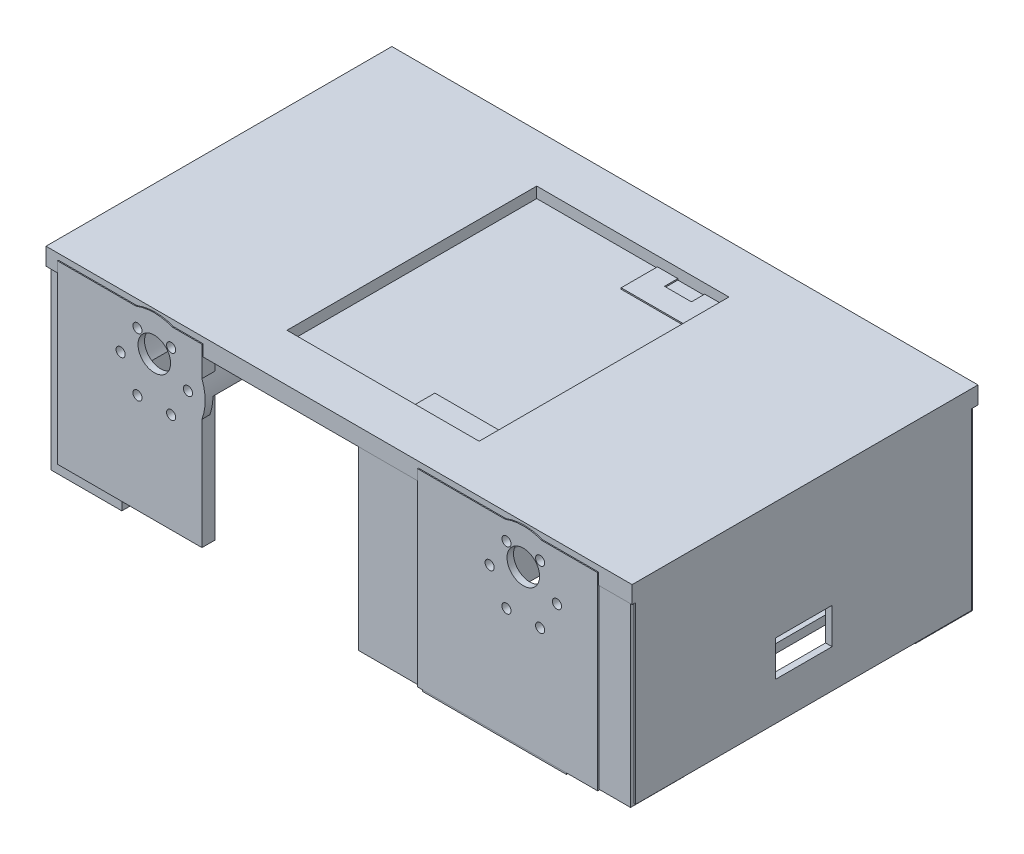
SolidWorks part; units mm, degrees
ref_plane "Front Plane" through (0, 0, 0) normal (0, 0, 1) x (1, 0, 0)
ref_plane "Top Plane" through (0, 0, 0) normal (0, 1, 0) x (1, 0, 0)
ref_plane "Right Plane" through (0, 0, 0) normal (1, 0, 0) x (0, 0, -1)
sketch "MotorHoldersSketch" plane through (0, 0, 0) normal (0, 0, 1) x (1, 0, 0)
  line L0 (0, 0) -> (170, 0) construction
  line L1 (0, 0) -> (0, 23.41) construction
  line L2 (170, 0) -> (170, 23.41) construction
  circle A0 centre (0, 0) radius 23.41
  circle A1 centre (170, 0) radius 23.41
ref_axis "MotorCenterAxis1" through (0, 0, 0) along (0, 0, 1)
ref_axis "MotorCenterAxis2" through (170, 0, 0) along (0, 0, 1)
extrude "MotorHolders" add sketch "MotorHoldersSketch" along normal blind 80 and the other way blind 80
sketch "Sketch3" plane through (0, 0, 0) normal (0, 0, 1) x (1, 0, 0)
  line L1 (1.9406, 21.133) -> (168.3435, 21.133)
  line L2 (1.9406, 21.133) -> (1.9406, 18.3155)
  line L3 (1.9406, 18.3155) -> (168.3435, 18.3155)
  line L4 (168.3435, 21.133) -> (168.3435, 18.3155)
sketch "Sketch4" plane through (0, 0, 0) normal (0, 1, 0) x (1, 0, 0)
  line L1 (221.2811, -76.3794) -> (-41.4939, -76.3794)
  line L2 (221.2811, -76.3794) -> (221.2811, 76.7331)
  line L3 (221.2811, 76.7331) -> (-41.4939, 76.7331)
  line L4 (-41.4939, -76.3794) -> (-41.4939, 76.7331)
extrude "Cut-Extrude1" cut sketch "Sketch4" against normal blind 23
ref_axis "Axis3" through (170, 0, 0) along (0, -1, 0)
sketch3d "ReferencePlanePosition"
  line L0 (170, 0, 0) -> (170, -34.8293, 0)
  line L1 (170, 0, 0) -> (170, -38.994, 0) construction
ref_plane "ReferencePlane" through (170, -34.8293, 0) normal (0, -1, 0) x (-1, 0, 0)
sketch "Sketch6" plane through (170, -34.8293, 0) normal (0, -1, 0) x (-1, 0, 0)
  line L1 (219.5858, 78.949) -> (187.0382, 78.949)
  line L2 (219.5858, 78.949) -> (219.5858, 52.706)
  line L3 (219.5858, 52.706) -> (187.0382, 52.706)
  line L4 (187.0382, 78.949) -> (187.0382, 52.706)
  line L5 (219.3147, -52.1095) -> (186.667, -52.1095)
  line L6 (219.3147, -52.1095) -> (219.3147, -78.2822)
  line L7 (219.3147, -78.2822) -> (186.667, -78.2822)
  line L8 (186.667, -52.1095) -> (186.667, -78.2822)
  line L9 (75.6651, 77.8627) -> (19.9904, 77.8627)
  line L10 (75.6651, 77.8627) -> (75.6651, 40.7512)
  line L11 (75.6651, 40.7512) -> (19.9904, 40.7512)
  line L12 (19.9904, 77.8627) -> (19.9904, 40.7512)
  line L13 (76.5596, -44.1716) -> (20.0852, -44.1716)
  line L14 (76.5596, -44.1716) -> (76.5596, -79.4437)
  line L15 (76.5596, -79.4437) -> (20.0852, -79.4437)
  line L16 (20.0852, -44.1716) -> (20.0852, -79.4437)
  line L17 (213.765, 71.7736) -> (201.9877, 71.7736)
  line L18 (213.765, 71.7736) -> (213.765, 60.5121)
  line L19 (213.765, 60.5121) -> (201.9877, 60.5121)
  line L20 (201.9877, 71.7736) -> (201.9877, 60.5121)
  line L21 (41.3552, 69.1777) -> (28.5109, 69.1777)
  line L22 (41.3552, 69.1777) -> (41.3552, 50.8413)
  line L23 (41.3552, 50.8413) -> (28.5109, 50.8413)
  line L24 (28.5109, 69.1777) -> (28.5109, 50.8413)
  line L25 (43.3068, -72.8101) -> (32.1723, -72.8101)
  line L26 (43.3068, -72.8101) -> (43.3068, -54.7747)
  line L27 (43.3068, -54.7747) -> (32.1723, -54.7747)
  line L28 (32.1723, -72.8101) -> (32.1723, -54.7747)
  line L29 (211.9411, -70.4881) -> (201.0982, -70.4881)
  line L30 (211.9411, -70.4881) -> (211.9411, -60.1404)
  line L31 (211.9411, -60.1404) -> (201.0982, -60.1404)
  line L32 (201.0982, -70.4881) -> (201.0982, -60.1404)
  line L37 (66.2772, 51.3198) -> (53.8697, 51.3198)
  line L38 (66.2772, 51.3198) -> (66.2772, 67.7632)
  line L39 (66.2772, 67.7632) -> (53.8697, 67.7632)
  line L40 (53.8697, 51.3198) -> (53.8697, 67.7632)
  line L45 (68.2481, -69.8638) -> (51.7107, -69.8638)
  line L46 (68.2481, -69.8638) -> (68.2481, -55.4273)
  line L47 (68.2481, -55.4273) -> (51.7107, -55.4273)
  line L48 (51.7107, -69.8638) -> (51.7107, -55.4273)
  line L49 (-20.7001, -79.4437) -> (-48.8506, -79.4437)
  line L50 (-20.7001, -79.4437) -> (-20.7001, -54.5097)
  line L51 (-20.7001, -54.5097) -> (-48.8506, -54.5097)
  line L52 (-48.8506, -79.4437) -> (-48.8506, -54.5097)
  line L53 (-18.3873, 77.8627) -> (-49.0581, 77.8627)
  line L54 (-18.3873, 77.8627) -> (-18.3873, 51.5325)
  line L55 (-18.3873, 51.5325) -> (-49.0581, 51.5325)
  line L56 (-49.0581, 77.8627) -> (-49.0581, 51.5325)
  line L57 (-41.8141, -72.8101) -> (-31.6362, -72.8101)
  line L58 (-41.8141, -72.8101) -> (-41.8141, -62.9794)
  line L59 (-41.8141, -62.9794) -> (-31.6362, -62.9794)
  line L60 (-31.6362, -72.8101) -> (-31.6362, -62.9794)
  line L61 (-31.6362, 69.1777) -> (-41.5347, 69.1777)
  line L62 (-31.6362, 69.1777) -> (-31.6362, 58.5421)
  line L63 (-31.6362, 58.5421) -> (-41.5347, 58.5421)
  line L64 (-41.5347, 69.1777) -> (-41.5347, 58.5421)
extrude "PowerBankHolders" add sketch "Sketch6" along normal blind 30 and the other way blind 55 separate body
sketch3d "3DSketch3"
  line L0 (170, 0, 0) -> (170, -64.5, 0) construction
ref_plane "Plane2" through (170, -64.5, 0) normal (0, -1, 0) x (-1, 0, 0)
sketch "Sketch7" plane through (170, -64.5, 0) normal (0, -1, 0) x (-1, 0, 0)
  line L1 (-9.5047, -80.801) -> (181.32, -80.801)
  line L2 (-9.5047, -80.801) -> (-9.5047, 73.8662)
  line L3 (-9.5047, 73.8662) -> (181.32, 73.8662)
  line L4 (181.32, -80.801) -> (181.32, 73.8662)
  line L5 (151.8712, -54.3972) -> (26.5361, -54.3972)
  line L6 (151.8712, -54.3972) -> (151.8712, 46.2413)
  line L7 (151.8712, 46.2413) -> (26.5361, 46.2413)
  line L8 (26.5361, -54.3972) -> (26.5361, 46.2413)
ref_point "Point1"
ref_point "Point2"
sketch3d "3DSketch11"
  line L0 (0, 0, -80) -> (170, 0, 80) construction
  point P4 (85, 0, 0)
sketch "MotorHolderExtrudeSketch" plane through (0, 0, 0) normal (0, 0, 1) x (1, 0, 0)
  circle A0 centre (170, 0) radius 20.415
  circle A1 centre (0, 0) radius 20.415
  circle A3 centre (0, 0) radius 23.41 construction
  circle A4 centre (170, 0) radius 23.41 construction
ref_point "TopOfMotors"
ref_plane "TangentToTopOfMotors" through (0, -20.415, 0) normal (0, 1, 0) x (1, 0, 0)
ref_axis "Axis4" through (85, 0, 0) along (0, -1, 0)
ref_plane "BottomOfPowerBankRegion" through (0, -20.425, 0) normal (0, 1, 0) x (1, 0, 0)
sketch "Sketch11" plane through (0, -20.425, 0) normal (0, 1, 0) x (1, 0, 0)
  line L0 (-18.9327, 3.7419) -> (188.9327, -3.7419) construction
  line L5 (-18.9327, -64.7581) -> (-18.9327, 72.2419)
  line L6 (188.9327, 63.7581) -> (188.9327, -71.2419)
  line L7 (188.9327, -71.2419) -> (-18.9327, -64.7581)
  line L8 (188.9327, 63.7581) -> (-18.9327, 72.2419)
  circle A0 centre (85, 0) radius 104 construction
ref_point "CenterAtBottomOfPowerBank"
ref_plane "TopOfPowerBankPlane" through (0, -54.425, 0) normal (0, 1, 0) x (1, 0, 0)
sketch "Sketch13" plane through (0, -54.425, 0) normal (0, 1, 0) x (1, 0, 0)
  line L1 (-19.4498, 72.5454) -> (166.1636, 72.5454)
  line L2 (-19.4498, 72.5454) -> (-19.4498, -78.2051)
  line L3 (-19.4498, -78.2051) -> (166.1636, -78.2051)
  line L4 (166.1636, 72.5454) -> (166.1636, -78.2051)
  line L5 (19.3173, -49.583) -> (137.9607, -49.583)
  line L6 (19.3173, -49.583) -> (19.3173, -21.0549)
  line L7 (19.3173, -21.0549) -> (137.9607, -21.0549)
  line L8 (137.9607, -49.583) -> (137.9607, -21.0549)
  line L9 (19.3173, 56.6778) -> (137.9607, 56.6778)
  line L10 (19.3173, 56.6778) -> (19.3173, 36.3234)
  line L11 (19.3173, 36.3234) -> (137.9607, 36.3234)
  line L12 (137.9607, 56.6778) -> (137.9607, 36.3234)
  line L13 (19.3173, 18.3186) -> (137.9607, 18.3186)
  line L14 (19.3173, 18.3186) -> (19.3173, -7.3615)
  line L15 (19.3173, -7.3615) -> (137.9607, -7.3615)
  line L16 (137.9607, 18.3186) -> (137.9607, -7.3615)
sketch "Sketch15" plane through (150.0096, 0, 0) normal (1, 0, 0) x (0, 0, -1)
  line L1 (72.5313, -25.7765) -> (45.7099, -25.7765)
  line L2 (72.5313, -25.7765) -> (72.5313, -24.2242)
  line L3 (72.5313, -24.2242) -> (45.7099, -24.2242)
  line L4 (45.7099, -25.7765) -> (45.7099, -24.2242)
extrude "PowerBankCut" cut sketch "Sketch11" against normal blind 64
ref_plane "Plane6" through (0, 0, 0) normal (0, 0, 1) x (1, 0, 0)
sketch "MotorGeometry1" plane through (0, 0, 0) normal (0, 0, 1) x (1, 0, 0)
  line L0 (170, 0) -> (170, -13.42)
  line L1 (170, 0) -> (170, -34.8293) construction
  line L2 (170, -13.42) -> (162.25, -13.42) construction
  line L3 (170, -13.42) -> (177.75, -13.42) construction
  line L4 (170, -13.42) -> (170, 7) construction
  line L5 (170, 0) -> (185.5, 0) construction
  line L6 (170, 0) -> (154.5, 0) construction
  line L7 (170, 0) -> (170, 13.42) construction
  line L8 (170, 0) -> (170, 23.41) construction
  line L9 (170, 13.42) -> (177.75, 13.42) construction
  line L10 (170, 13.42) -> (162.25, 13.42)
ref_axis "BoltAxisA" through (185.5, 0, 0) along (0, 0, 1)
ref_axis "BoltAxisB" through (177.75, -13.42, 0) along (0, 0, 1)
ref_axis "BoltAxisC" through (162.25, -13.42, 0) along (0, 0, 1)
ref_axis "BoltAxisD" through (154.5, 0, 0) along (0, 0, 1)
ref_axis "BoltAxisE" through (162.25, 13.42, 0) along (0, 0, 1)
ref_axis "BoltAxisF" through (177.75, 13.42, 0) along (0, 0, 1)
ref_point "Point6"
ref_point "Point7"
ref_point "Point8"
ref_point "Point9"
ref_point "Point10"
ref_point "Point11"
ref_point "Point12"
ref_point "Point13"
ref_point "Point14"
ref_point "Point15"
ref_point "Point16"
ref_point "Point17"
ref_plane "Plane7" through (0, 0, 0) normal (0, 0, 1) x (1, 0, 0)
sketch "MotorGeometry2" plane through (0, 0, 0) normal (0, 0, 1) x (1, 0, 0)
  line L0 (0, 0) -> (0, -13.42) construction
  line L1 (0, -13.42) -> (7.75, -13.42) construction
  line L2 (0, -13.42) -> (-7.75, -13.42) construction
  line L3 (0, 0) -> (0, 13.42)
  line L4 (0, -13.42) -> (0, 7) construction
  line L5 (0, 13.42) -> (7.75, 13.42) construction
  line L6 (0, 13.42) -> (-7.75, 13.42) construction
  line L7 (0, 0) -> (15.5, 0) construction
  line L8 (0, 0) -> (-15.5, 0) construction
  line L9 (0, 0) -> (0, 23.41) construction
ref_axis "Axis11" through (15.5, 0, 0) along (0, 0, 1)
ref_axis "Axis12" through (7.75, 13.42, 0) along (0, 0, 1)
ref_axis "Axis13" through (-7.75, 13.42, 0) along (0, 0, 1)
ref_axis "Axis14" through (-15.5, 0, 0) along (0, 0, 1)
ref_axis "Axis15" through (-7.75, -13.42, 0) along (0, 0, 1)
ref_axis "Axis16" through (7.75, -13.42, 0) along (0, 0, 1)
ref_point "Point18"
ref_point "Point19"
ref_point "Point20"
ref_point "Point21"
ref_point "Point22"
ref_point "Point23"
ref_point "Point24"
ref_point "Point25"
ref_point "Point26"
ref_point "Point27"
ref_point "Point28"
ref_point "Point29"
ref_plane "BottomPlane" through (0, 19.575, 0) normal (0, 1, 0) x (1, 0, 0)
ref_axis "OutputShaftReference1" through (0, 7, 0) along (0, 0, 1)
ref_axis "OutputShaftReference2" through (170, 7, 0) along (0, 0, 1)
sketch "Sketch21" plane through (0, 19.575, 0) normal (0, 1, 0) x (1, 0, 0)
  line L0 (219.6842, -79.5488) -> (-50.341, -79.5488)
  line L1 (-50.341, -79.5488) -> (-50.341, 79.7899)
  line L2 (-50.341, 79.7899) -> (219.6842, 79.7899)
  line L3 (219.6842, 79.7899) -> (219.6842, -79.5488)
  line L4 (127.2472, -57.5918) -> (127.2472, 57.4773)
  line L5 (127.2472, 57.4773) -> (38.7099, 57.4773)
  line L6 (38.7099, 57.4773) -> (38.7099, -57.5918)
  line L7 (38.7099, -57.5918) -> (127.2472, -57.5918)
extrude "BottomPlate" add sketch "Sketch21" along normal blind 5 and the other way blind 3
ref_plane "HoleReferencePlane1" through (0, 0, 80) normal (0, 0, 1) x (1, 0, 0)
ref_point "OutputShaftPosition3"
ref_point "OutputShaftPosition1"
sketch "Sketch23" plane through (0, 0, 80) normal (0, 0, 1) x (1, 0, 0)
  line L1 (21.9586, -59.3229) -> (-44.5901, -59.3229)
  line L2 (21.9586, -59.3229) -> (21.9586, 21.8402)
  line L3 (21.9586, 21.8402) -> (-44.5901, 21.8402)
  line L4 (-44.5901, -59.3229) -> (-44.5901, 21.8402)
  line L5 (121.3218, 21.8402) -> (204.258, 21.8402)
  line L6 (121.3218, 21.8402) -> (121.3218, -65.2231)
  line L7 (121.3218, -65.2231) -> (204.258, -65.2231)
  line L8 (204.258, 21.8402) -> (204.258, -65.2231)
extrude "MotorMountingSupport1" add sketch "Sketch23" against normal blind 6
ref_plane "HoleReferencePlane2" through (0, 0, -80) normal (0, 0, -1) x (-1, 0, 0)
ref_point "OutputShaftPosition4"
ref_point "OutputShaftPosition2"
sketch "Sketch24" plane through (0, 0, -80) normal (0, 0, -1) x (-1, 0, 0)
  line L1 (-202.1905, -67.1257) -> (-139.5471, -67.1257)
  line L2 (-202.1905, -67.1257) -> (-202.1905, 19.2374)
  line L3 (-202.1905, 19.2374) -> (-139.5471, 19.2374)
  line L4 (-139.5471, -67.1257) -> (-139.5471, 19.2374)
  line L5 (-24.3642, -64.1521) -> (29.5505, -64.1521)
  line L6 (-24.3642, -64.1521) -> (-24.3642, 22.5226)
  line L7 (-24.3642, 22.5226) -> (29.5505, 22.5226)
  line L8 (29.5505, -64.1521) -> (29.5505, 22.5226)
extrude "MotorMountingSuppor2" add sketch "Sketch24" against normal blind 6
sketch "Sketch17" plane through (0, 0, 80) normal (0, 0, 1) x (1, 0, 0)
  circle A0 centre (185.5, 0) radius 2.1
  circle A1 centre (177.75, -13.42) radius 2.1
  circle A2 centre (162.25, -13.42) radius 2.1
  circle A3 centre (154.5, 0) radius 2.1
  circle A4 centre (162.25, 13.42) radius 2.1
  circle A5 centre (177.75, 13.42) radius 2.1
  circle A6 centre (170, 7) radius 7.5
extrude "MotorHoles1" cut sketch "Sketch17" against normal blind 31.5
sketch "Sketch19" plane through (0, 0, -80) normal (0, 0, -1) x (-1, 0, 0)
  circle A0 centre (-185.5, 0) radius 2.1
  circle A1 centre (-177.75, -13.42) radius 2.1
  circle A2 centre (-162.25, -13.42) radius 2.1
  circle A3 centre (-154.5, 0) radius 2.1
  circle A4 centre (-162.25, 13.42) radius 2.1
  circle A5 centre (-177.75, 13.42) radius 2.1
  circle A6 centre (-170, 7) radius 7.5
extrude "MotorHoles2" cut sketch "Sketch19" against normal blind 31.5
sketch "BoltHolesSketch3" plane through (0, 0, 80) normal (0, 0, 1) x (1, 0, 0)
  circle A0 centre (7.75, -13.42) radius 2.1
  circle A1 centre (15.5, 0) radius 2.1
  circle A2 centre (7.75, 13.42) radius 2.1
  circle A3 centre (-7.75, 13.42) radius 2.1
  circle A4 centre (-15.5, 0) radius 2.1
  circle A5 centre (-7.75, -13.42) radius 2.1
  circle A6 centre (0, 7) radius 7.5
extrude "MotorHoles3" cut sketch "BoltHolesSketch3" against normal blind 31.5
sketch "BoltHolesSketch4" plane through (0, 0, -80) normal (0, 0, -1) x (-1, 0, 0)
  circle A0 centre (-15.5, 0) radius 2.1
  circle A1 centre (-7.75, 13.42) radius 2.1
  circle A2 centre (7.75, 13.42) radius 2.1
  circle A3 centre (15.5, 0) radius 2.1
  circle A4 centre (7.75, -13.42) radius 2.1
  circle A5 centre (-7.75, -13.42) radius 2.1
  circle A6 centre (0, 7) radius 7.5
extrude "MotorHoles4" cut sketch "BoltHolesSketch4" against normal blind 15
ref_plane "Front" through (219.6842, 0, 0) normal (1, 0, 0) x (0, 0, -1)
sketch "Sketch29" plane through (219.6842, 0, 0) normal (1, 0, 0) x (0, 0, -1)
  line L1 (76.6955, -63.9254) -> (-77.9397, -63.9254)
  line L2 (76.6955, -63.9254) -> (76.6955, 20.2062)
  line L3 (76.6955, 20.2062) -> (-77.9397, 20.2062)
  line L4 (-77.9397, -63.9254) -> (-77.9397, 20.2062)
  line L5 (-13.4507, -46.2559) -> (12.5493, -46.2559)
  line L6 (-13.4507, -46.2559) -> (-13.4507, -29.7559)
  line L7 (-13.4507, -29.7559) -> (12.5493, -29.7559)
  line L8 (12.5493, -46.2559) -> (12.5493, -29.7559)
extrude "Boss-Extrude8" add sketch "Sketch29" against normal blind 3
extrude "MotorHolderCut" cut sketch "MotorHolderExtrudeSketch" against normal blind 77 and the other way blind 77
ref_plane "RaspberryPiBasePlane" through (0, 16.575, 0) normal (0, -1, 0) x (-1, 0, 0)
sketch "Sketch27" plane through (0, 16.575, 0) normal (0, -1, 0) x (-1, 0, 0)
  line L1 (31.6337, 64.5517) -> (-194.8264, 64.5517)
  line L2 (31.6337, 64.5517) -> (31.6337, -65.4335)
  line L3 (31.6337, -65.4335) -> (-194.8264, -65.4335)
  line L4 (-194.8264, 64.5517) -> (-194.8264, -65.4335)
extrude "Boss-Extrude6" add sketch "Sketch27" against normal blind 3
ref_plane "Plane12" through (0, -64.8293, 0) normal (0, -1, 0) x (-1, 0, 0)
sketch "Sketch28" plane through (0, -64.8293, 0) normal (0, -1, 0) x (-1, 0, 0)
  line L1 (-189.3897, -79.549) -> (-123.0026, -79.549)
  line L2 (-189.3897, -79.549) -> (-189.3897, 78.1499)
  line L3 (-189.3897, 78.1499) -> (-123.0026, 78.1499)
  line L4 (-123.0026, -79.549) -> (-123.0026, 78.1499)
extrude "Boss-Extrude7" add sketch "Sketch28" along normal blind 1.5 and the other way blind 2.5
